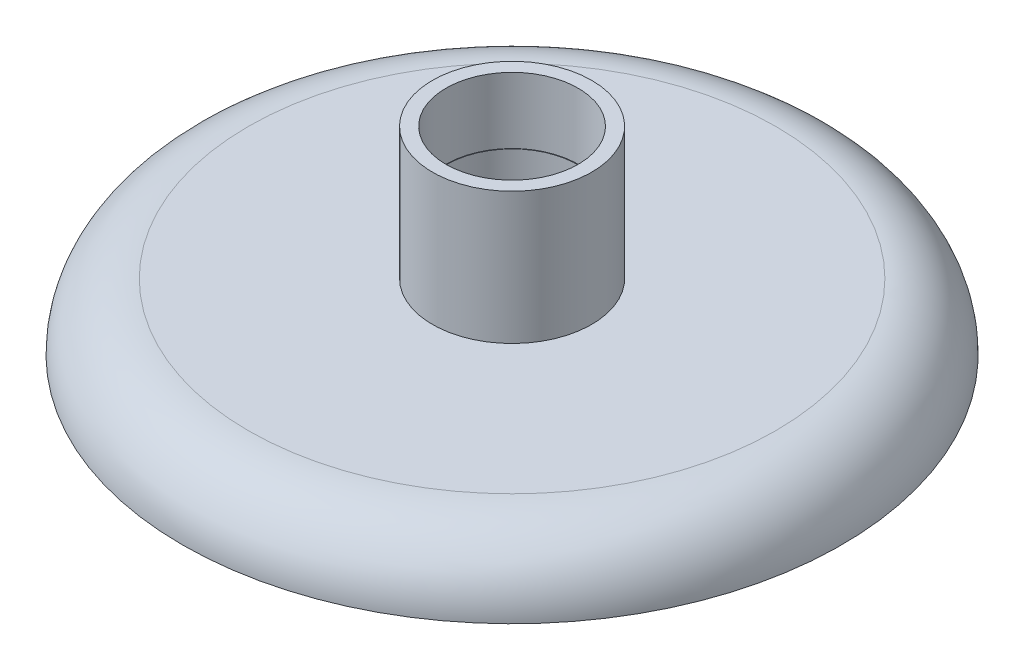
SolidWorks part; units mm, degrees
ref_plane "Front Plane" through (0, 0, 0) normal (0, 0, 1) x (1, 0, 0)
ref_plane "Top Plane" through (0, 0, 0) normal (0, 1, 0) x (1, 0, 0)
ref_plane "Right Plane" through (0, 0, 0) normal (1, 0, 0) x (0, 0, -1)
sketch "Sketch1" plane through (0, 0, 0) normal (0, 1, 0) x (1, 0, 0)
  circle A0 centre (0, 0) radius 63.4753
extrude "Boss-Extrude1" add sketch "Sketch1" along normal blind 12.7
fillet "Fillet2" radius 12.7 1 edges at (0, 12.7, 63.4753)
shell "Shell2" thickness 6.35 removed face at (0, 0, 63.4753)
sketch "Sketch2" plane through (0, 0, 0) normal (0, 1, 0) x (1, 0, 0)
  circle A0 centre (0, 0) radius 12.71
extrude "Cut-Extrude1" cut sketch "Sketch2" along normal blind 12.7
sketch "Sketch3" plane through (0, 0, 0) normal (0, 1, 0) x (1, 0, 0)
sketch "Sketch4" plane through (0, 12.7, 0) normal (0, 1, 0) x (1, 0, 0)
  circle A0 centre (0, 0) radius 15.3312
extrude "Boss-Extrude2" add sketch "Sketch4" along normal blind 25.4
sketch "Sketch5" plane through (0, 0, 0) normal (0, 1, 0) x (1, 0, 0)
  circle A0 centre (0, 0) radius 12.6202
extrude "Cut-Extrude2" cut sketch "Sketch5" along normal blind 27.94
ref_plane "Plane2" through (0, 33.02, 0) normal (0, 1, 0) x (1, 0, 0)
sketch "Sketch9" plane through (0, 33.02, 0) normal (0, 1, 0) x (1, 0, 0)
  circle A0 centre (0, 0) radius 15.3312
curve "Helix/Spiral1" pitch 5.08 height 15.24 turns 3
sketch "Sketch11" plane through (0, 38.1, 0) normal (0, 1, 0) x (1, 0, 0)
  circle A0 centre (0, 0) radius 12.7236
extrude "Cut-Extrude4" cut sketch "Sketch11" against normal blind 12.7
